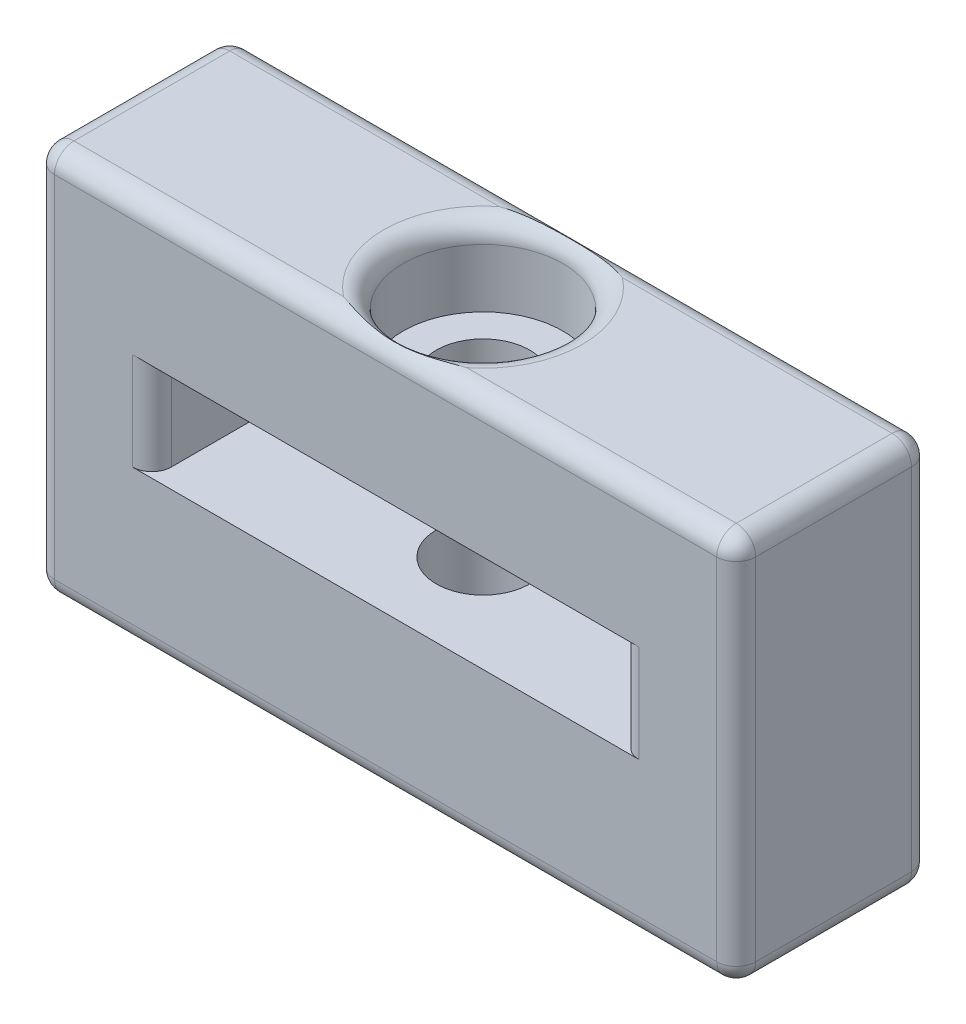
SolidWorks part; units mm, degrees
ref_plane "Front Plane" through (0, 0, 0) normal (0, 0, 1) x (1, 0, 0)
ref_plane "Top Plane" through (0, 0, 0) normal (0, 1, 0) x (1, 0, 0)
ref_plane "Right Plane" through (0, 0, 0) normal (1, 0, 0) x (0, 0, -1)
sketch "Sketch1" plane through (0, 0, 0) normal (0, 1, 0) x (1, 0, 0)
  line L5 (-6, -2.5) -> (6, -2.5)
  line L6 (-6, -2.5) -> (-6, 2.5)
  line L7 (-6, 2.5) -> (6, 2.5)
  line L8 (6, -2.5) -> (6, 2.5)
  line L9 (-6, -2.5) -> (6, 2.5) construction
  line L10 (-6, 2.5) -> (6, -2.5) construction
  point P0 (0, 0)
  dimension "D1" = 12
  dimension "D2" = 5
extrude "Boss-Extrude1" add sketch "Sketch1" along normal blind 4
sketch "Sketch2" plane through (0, 0, 2.5) normal (0, 0, 1) x (1, 0, 0)
  line L0 (6, 4) -> (6, 0) construction
  line L2 (-6, 0) -> (-6, 6.5)
  line L4 (6, 0) -> (6, 6.5)
  line L5 (6, 6.5) -> (9, 6.5)
  line L6 (9, 6.5) -> (9, 0)
  line L7 (9, 0) -> (6, 0)
  line L8 (-6, 0) -> (-9, 0)
  line L9 (-9, 0) -> (-9, 6.5)
  line L10 (-9, 6.5) -> (-6, 6.5)
  line L11 (-6, 0) -> (6, 0) construction
  point P9 (6, 7.9061)
  point P15 (-6, 7.7646)
  dimension "D1" = 6.5
  dimension "D2" = 3
  dimension "D3" = 3
extrude "Boss-Extrude2" add sketch "Sketch2" against normal up to surface (5 mm away) up to face at (0, 2, -2.5)
sketch "Sketch3" plane through (0, 6.5, 0) normal (0, 1, 0) x (1, 0, 0)
  line L1 (-9, 2.5) -> (9, 2.5)
  line L2 (-9, 2.5) -> (-9, -2.5)
  line L3 (-9, -2.5) -> (9, -2.5)
  line L4 (9, 2.5) -> (9, -2.5)
extrude "Boss-Extrude3" add sketch "Sketch3" along normal blind 3.5
sketch "Sketch4" plane through (0, 10, 0) normal (0, 1, 0) x (1, 0, 0)
  line L0 (9, 2.5) -> (-9, -2.5) construction
  circle A0 centre (0, 0) radius 1.2
  dimension "D1" = 2.4
extrude "Cut-Extrude1" cut sketch "Sketch4" against normal up to surface (10 mm away) up to face at (0, 0, 0)
sketch "Sketch5" plane through (0, 10, 0) normal (0, 1, 0) x (1, 0, 0)
  circle A0 centre (0, 0) radius 2.05
  dimension "D1" = 4.1
extrude "Cut-Extrude2" cut sketch "Sketch5" against normal blind 2
fillet "Fillet1" radius 0.5 17 edges at (9, 5, -2.5) (6, 5.25, -2.5) (-6, 5.25, -2.5) (-9, 5, -2.5) (-9, 5, 2.5) (-6, 5.25, 2.5) (6, 5.25, 2.5) (9, 5, 2.5) (9, 10, 0) (-9, 10, 0) (0, 10, 2.5) (0, 10, -2.5) (0, 10, 2.05) (9, 0, 0) (0, 0, -2.5) (-9, 0, 0) (0, 0, 2.5)
